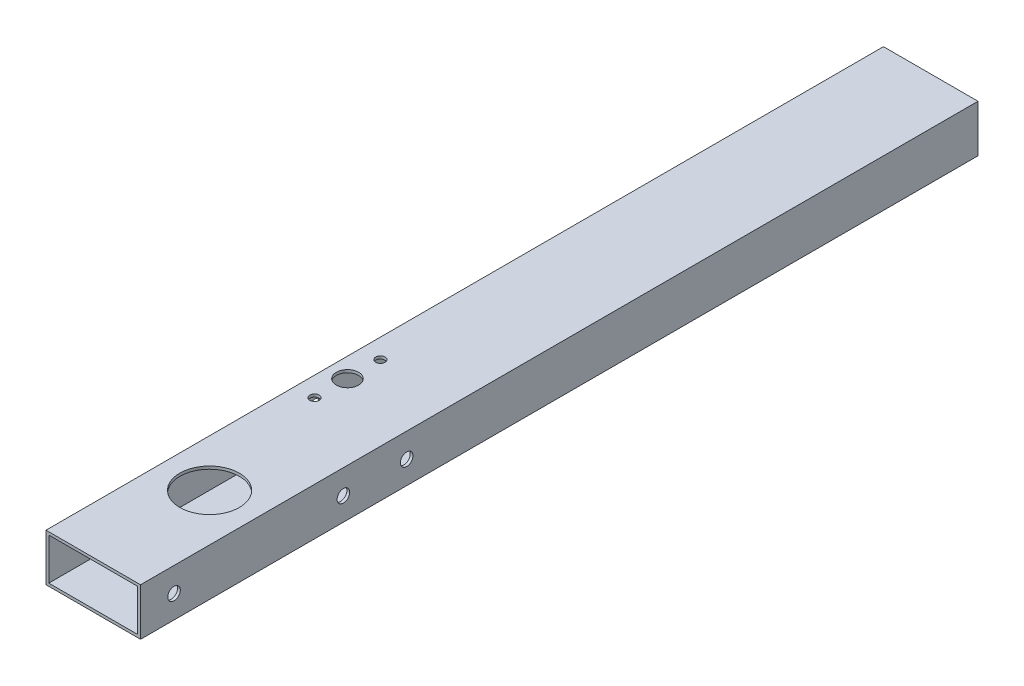
SolidWorks part; units mm, degrees
material "AISI 1015 Acero estirado en frío (SS)"
ref_plane "Alzado" through (0, 0, 0) normal (0, 0, 1) x (1, 0, 0)
ref_plane "Planta" through (0, 0, 0) normal (0, 1, 0) x (1, 0, 0)
ref_plane "Vista lateral" through (0, 0, 0) normal (1, 0, 0) x (0, 0, -1)
sketch "Croquis1" plane through (0, 0, 0) normal (0, 0, 1) x (1, 0, 0)
  line L0 (-23.9, 11.2) -> (23.9, 11.2)
  line L1 (-25.4, -12.7) -> (25.4, -12.7)
  line L2 (-25.4, -12.7) -> (-25.4, 12.7)
  line L3 (-25.4, 12.7) -> (25.4, 12.7)
  line L4 (25.4, -12.7) -> (25.4, 12.7)
  line L5 (-25.4, -12.7) -> (25.4, 12.7) construction
  line L6 (-25.4, 12.7) -> (25.4, -12.7) construction
  line L7 (23.9, -11.2) -> (23.9, 11.2)
  line L8 (-23.9, -11.2) -> (23.9, -11.2)
  line L9 (-23.9, -11.2) -> (-23.9, 11.2)
  point P0 (0, 0)
  dimension "D1" = 25.4
  dimension "D2" = 50.8
  dimension "D3" = 1.5
extrude "Saliente-Extruir1" add sketch "Croquis1" along normal blind 450
ref_plane "Plano1" through (0, 12.7, 0) normal (0, 1, 0) x (1, 0, 0)
sketch "Croquis2" plane through (0, 12.7, 0) normal (0, 1, 0) x (1, 0, 0)
  line L0 (0, -450) -> (0, -262.1851) construction
  line L1 (25.4, -450) -> (-25.4, -450) construction
  line L2 (25.4, -387.5) -> (-25.7584, -387.5) construction
  line L3 (25.4, -450) -> (25.4, 0) construction
  circle A0 centre (0, -387.5) radius 16
  dimension "D2" = 32
  dimension "D1" = 62.5
extrude "Cortar-Extruir1" cut sketch "Croquis2" against normal blind 26
hole_wizard "Taladro de margen para 1/42" positions "Croquis5" profile "Croquis6" hole size "1/4" standard "Ansi Inch" end condition through all
sketch "Croquis5" plane through (-26.4, 572.4886, 162.9891) normal (-1, 0, 0) x (0, -1, 0)
  point P0 (572.8886, 269.0109)
  point P1 (572.8886, 178.0109)
  point P2 (572.8886, 144.0109)
sketch "Croquis6" plane through (-26.4, -0.4, 432) normal (0, 1, 0) x (0, 0, 1)
  line L0 (0, 0) -> (0, 51.8)
  line L1 (0, 51.8) -> (3.3782, 51.8)
  line L2 (3.3782, 51.8) -> (3.3782, 0)
  line L3 (3.3782, 0) -> (0, 0)
  line L4 (0, -6.35) -> (0, 107.95) construction
  dimension "Diámetro de taladro hasta el siguiente" = 6.7564
  dimension "Profundidad de taladro hasta el siguiente" = 51.8
sketch "Croquis7" plane through (0, 12.7, 0) normal (0, 1, 0) x (1, 0, 0)
  line L0 (25.4, -298.5) -> (-25.4, -298.5) construction
  line L1 (25.4, -450) -> (25.4, 0) construction
  line L2 (-25.4, -450) -> (-25.4, 0) construction
  line L3 (-14.9, -280.8) -> (-14.9, -316.2) construction
  circle A0 centre (-14.9, -298.5) radius 6
  circle A1 centre (-14.9, -280.8) radius 2.5
  circle A2 centre (-14.9, -316.2) radius 2.5
  point P6 (0, -387.5)
  point P11 (-14.9, -298.5)
  dimension "D4" = 5
  dimension "D5" = 12
  dimension "D1" = 89
  dimension "D2" = 10.5
  dimension "D3" = 35.4
extrude "Cortar-Extruir2" cut sketch "Croquis7" against normal up to surface (25.4 mm away) up to face at (0, -12.7, 403.5)
